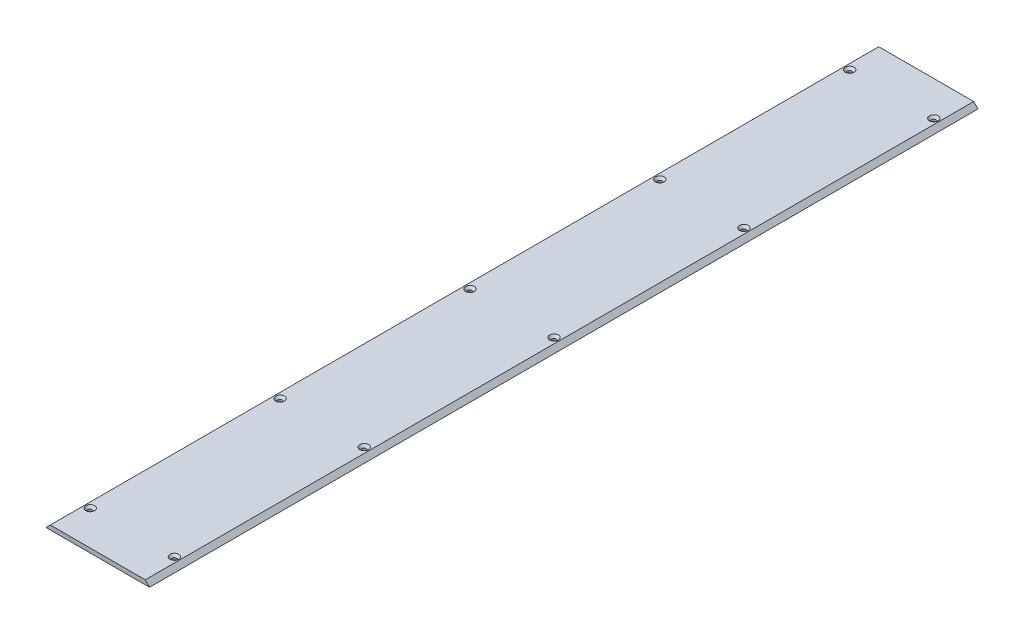
SolidWorks part; units mm, degrees
ref_plane "Front Plane" through (0, 0, 0) normal (0, 0, 1) x (1, 0, 0)
ref_plane "Top Plane" through (0, 0, 0) normal (0, 1, 0) x (1, 0, 0)
ref_plane "Right Plane" through (0, 0, 0) normal (1, 0, 0) x (0, 0, -1)
sketch "Sketch1" plane through (0, 0, 0) normal (0, 1, 0) x (1, 0, 0)
  line L1 (0, 0) -> (152.4, 0)
  line L2 (0, 0) -> (0, 1219.2)
  line L3 (0, 1219.2) -> (152.4, 1219.2)
  line L4 (152.4, 0) -> (152.4, 1219.2)
  dimension "D1" = 152.4
  dimension "D2" = 1219.2
extrude "Boss-Extrude1" add sketch "Sketch1" along normal blind 6.35
hole_wizard "CSK for 1/4 Flat Head Machine Screw1" positions "Sketch2" profile "Sketch3" countersink size "1/4" standard "ANSI Inch" end condition through all
sketch "Sketch2" plane through (0, 6.35, 0) normal (0, 1, 0) x (1, 0, 0)
  line L0 (14.2875, 1168.4) -> (14.2875, 889) construction
  line L1 (76.2, 1219.2) -> (76.2, 0) construction
  line L2 (152.4, 1219.2) -> (0, 1219.2) construction
  line L3 (0, 0) -> (152.4, 0) construction
  line L4 (0, 609.6) -> (152.4, 609.6) construction
  line L5 (0, 1219.2) -> (0, 0) construction
  line L6 (152.4, 0) -> (152.4, 1219.2) construction
  point P0 (14.2875, 1168.4)
  point P8 (138.1125, 1168.4)
  point P9 (138.1125, 889)
  point P10 (138.1125, 609.6)
  point P11 (138.1125, 330.2)
  point P12 (138.1125, 50.8)
  point P13 (14.2875, 889)
  point P14 (14.2875, 609.6)
  point P15 (14.2875, 330.2)
  point P16 (14.2875, 50.8)
  dimension "D3" = 279.4
  dimension "D4" = 14.2875
  dimension "D1" = 2
  dimension "D2" = 5
sketch "Sketch3" plane through (14.2875, 6.35, -1168.4) normal (1, 0, 0) x (0, 0, 1)
  line L0 (0, 0) -> (0, 6.35)
  line L1 (0, 6.35) -> (3.3782, 6.35)
  line L2 (3.3782, 6.35) -> (3.3782, 3.5209)
  line L3 (3.3782, 3.5209) -> (6.4389, 0)
  line L5 (6.4389, 0) -> (0, 0)
  line L6 (-3.3782, 3.5209) -> (-6.4389, 0) construction
  line L11 (0, -6.35) -> (0, 107.95) construction
  dimension "Thru Hole Dia." = 6.7564
  dimension "Thru Hole Depth" = 6.35
  dimension "Near C'Sink Dia." = 12.8778
  dimension "Near C'Sink Angle" = 82
chamfer "Chamfer1" distance 6.35 angle 45 2 edges at (0, 6.35, -609.6) (152.4, 6.35, -609.6)
